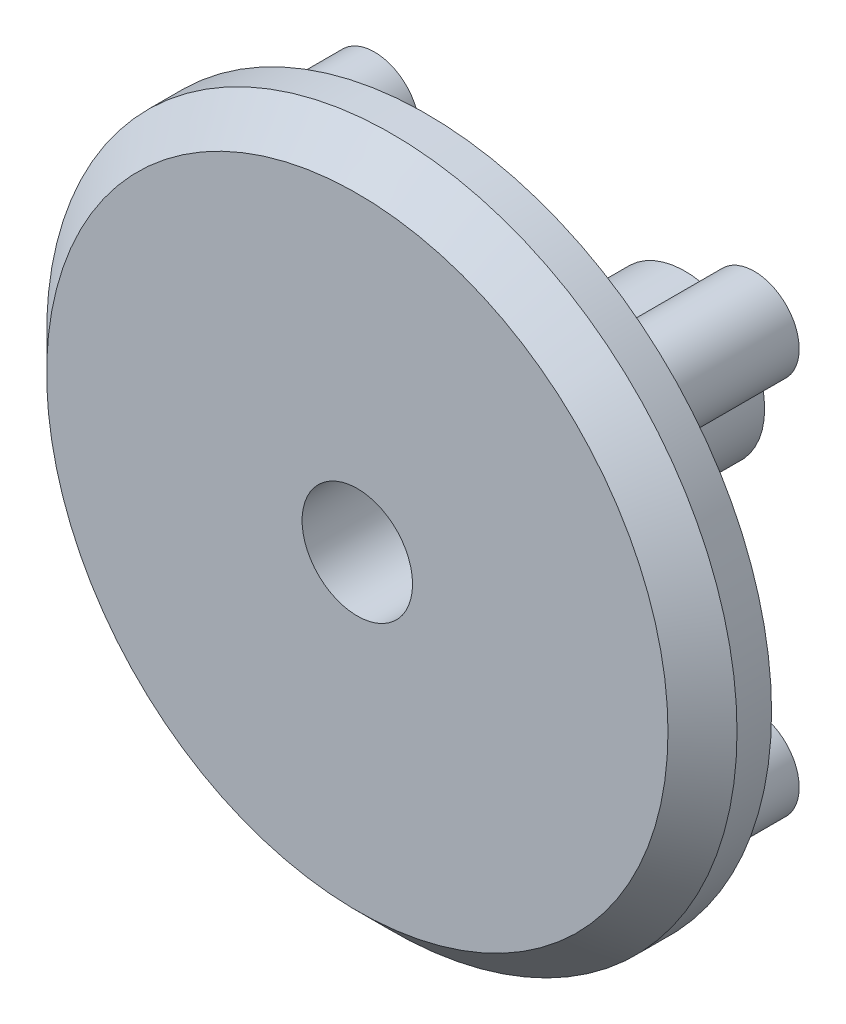
SolidWorks part; units mm, degrees
ref_plane "Front Plane" through (0, 0, 0) normal (0, 0, 1) x (1, 0, 0)
ref_plane "Top Plane" through (0, 0, 0) normal (0, 1, 0) x (1, 0, 0)
ref_plane "Right Plane" through (0, 0, 0) normal (1, 0, 0) x (0, 0, -1)
ref_axis "X" through (-88.99, 0, 0) along (1, 0, 0)
ref_axis "Y" through (0, 55, 0) along (0, -1, 0)
ref_axis "Z" through (0, 0, -88.99) along (0, 0, 1)
sketch "Sketch1" plane through (0, 0, 0) normal (0, 0, 1) x (1, 0, 0)
  line L1 (-5.5, 5.5) -> (5.5, 5.5) construction
  line L2 (-5.5, 5.5) -> (-5.5, -5.5) construction
  line L3 (-5.5, -5.5) -> (5.5, -5.5) construction
  line L4 (5.5, 5.5) -> (5.5, -5.5) construction
  line L5 (-5.5, 5.5) -> (5.5, -5.5) construction
  line L6 (-5.5, -5.5) -> (5.5, 5.5) construction
  circle A0 centre (0, 0) radius 2.3
  circle A1 centre (5.5, 5.5) radius 1.3
  circle A2 centre (5.5, -5.5) radius 1.3
  circle A3 centre (-5.5, -5.5) radius 1.3
  circle A4 centre (-5.5, 5.5) radius 1.3
  circle A5 centre (0, 0) radius 10
  circle A6 centre (0, 0) radius 1.6
  point P0 (0, 0)
  dimension "D2" = 4.6
  dimension "D3" = 2.6
  dimension "D4" = 20
  dimension "D5" = 3.2
  dimension "D1" = 11
extrude "Boss-Extrude1" add sketch "Sketch1" along normal blind 2 contours A5 | A6
extrude "Boss-Extrude2" add sketch "Sketch1<3>" against normal blind 4 contours A4 | A1 | A2 | A3 region at (5.5, 5.5, 0) region at (5.5, -5.5, 0) region at (-5.5, -5.5, 0) region at (-5.5, 5.5, 0)
sketch "Sketch1<3>" plane through (0, 0, 0) normal (0, 0, 1) x (1, 0, 0) same geometry as "Sketch1"
chamfer "Chamfer1" distance 1 angle 45 1 edges at (10, 0, 2)
extrude "Boss-Extrude4" add sketch "Sketch1<5>" against normal blind 7.5 contours A0 A6 region at (-2.2349, 0, 0)
sketch "Sketch1<5>" plane through (0, 0, 0) normal (0, 0, 1) x (1, 0, 0) same geometry as "Sketch1"
